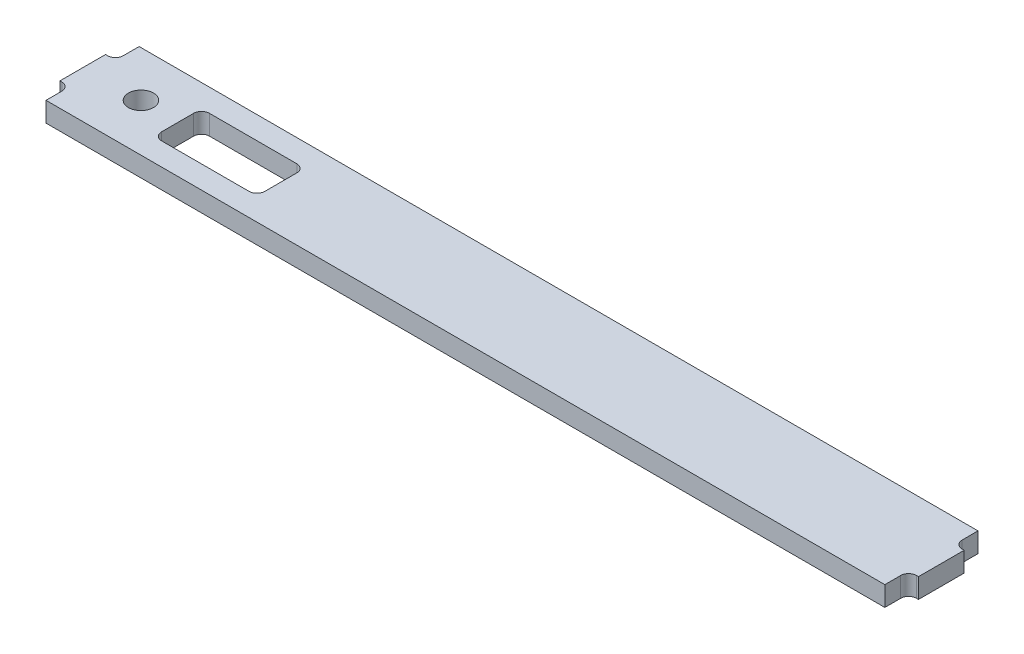
SolidWorks part; units mm, degrees
ref_plane "Front Plane" through (0, 0, 0) normal (0, 0, 1) x (1, 0, 0)
ref_plane "Top Plane" through (0, 0, 0) normal (0, 1, 0) x (1, 0, 0)
ref_plane "Right Plane" through (0, 0, 0) normal (1, 0, 0) x (0, 0, -1)
sketch "Sketch1" plane through (0, 0, 0) normal (0, 1, 0) x (1, 0, 0)
  line L1 (336.55, 37.3714) -> (-336.55, 37.3714)
  line L2 (336.55, 37.3714) -> (336.55, -37.3714)
  line L3 (336.55, -37.3714) -> (-336.55, -37.3714)
  line L4 (-336.55, 37.3714) -> (-336.55, -37.3714)
  line L5 (336.55, 37.3714) -> (-336.55, -37.3714) construction
  line L6 (336.55, -37.3714) -> (-336.55, 37.3714) construction
  point P0 (0, 0)
  dimension "D1" = 673.1
  dimension "D2" = 74.7428
extrude "Boss-Extrude1" add sketch "Sketch1" along normal blind 15.875
sketch "Sketch2" plane through (0, 15.875, 0) normal (0, 1, 0) x (1, 0, 0)
  line L0 (336.55, 37.3714) -> (-336.55, 37.3714) construction
  line L1 (344.4875, 18.3214) -> (-344.4875, 18.3214)
  line L2 (344.4875, 18.3214) -> (344.4875, -18.3214)
  line L3 (344.4875, -18.3214) -> (-344.4875, -18.3214)
  line L4 (-344.4875, 18.3214) -> (-344.4875, -18.3214)
  line L5 (344.4875, 18.3214) -> (-344.4875, -18.3214) construction
  line L6 (344.4875, -18.3214) -> (-344.4875, 18.3214) construction
  line L7 (-336.55, 37.3714) -> (-336.55, -37.3714) construction
  point P0 (0, 0)
  dimension "D1" = 19.05
  dimension "D2" = 7.9375
extrude "Boss-Extrude2" [suppressed] add sketch "Sketch2" against normal up to surface (15.875 mm away) up to face at (0, 0, 0)
fillet "Fillet1" [suppressed] radius 6.35
sketch "Sketch3" plane through (0, 15.875, 0) normal (0, 1, 0) x (1, 0, 0)
  line L0 (-336.55, -37.3714) -> (336.55, -37.3714) construction
  line L2 (-336.55, 37.3714) -> (-336.55, -37.3714) construction
  circle A0 centre (-298.45, 0.7286) radius 10.1
  dimension "D3" = 20.2
  dimension "D1" = 38.1
  dimension "D2" = 38.1
extrude "Cut-Extrude1" cut sketch "Sketch3" against normal through all both and the other way through all
sketch "Sketch4" plane through (0, 15.875, 0) normal (0, 1, 0) x (1, 0, 0)
  line L0 (-336.55, 37.3714) -> (-336.55, -37.3714) construction
  line L1 (-336.55, 18.3214) -> (-344.4875, 18.3214)
  line L2 (-336.55, 18.3214) -> (-336.55, -18.3214)
  line L3 (-336.55, -18.3214) -> (-344.4875, -18.3214)
  line L4 (-344.4875, 18.3214) -> (-344.4875, -18.3214)
  line L5 (336.55, 37.3714) -> (-336.55, 37.3714) construction
  line L6 (-336.55, -37.3714) -> (336.55, -37.3714) construction
  line L7 (0, -5.1837) -> (0, 37.3714) construction
  line L8 (344.4875, 18.3214) -> (344.4875, -18.3214)
  line L9 (336.55, -18.3214) -> (344.4875, -18.3214)
  line L10 (336.55, 18.3214) -> (336.55, -18.3214)
  line L11 (336.55, 18.3214) -> (344.4875, 18.3214)
  dimension "D1" = 19.05
  dimension "D2" = 19.05
  dimension "D3" = 7.9375
  dimension "D4" = 688.975
extrude "Boss-Extrude3" add sketch "Sketch4" against normal up to surface (15.875 mm away) up to face at (-298.45, 0, 9.3714)
fillet "Fillet2" radius 6.35 4 edges at (336.55, 7.9375, 18.3214) (336.55, 7.9375, -18.3214) (-336.55, 7.9375, 18.3214) (-336.55, 7.9375, -18.3214)
sketch "Sketch5" plane through (0, 15.875, 0) normal (0, 1, 0) x (1, 0, 0)
  line L0 (0, 0) -> (-185.4835, 0) construction
  line L1 (-268.2875, -19.177) -> (-185.4835, -19.177)
  line L2 (-268.2875, -19.177) -> (-268.2875, 19.177)
  line L3 (-268.2875, 19.177) -> (-185.4835, 19.177)
  line L4 (-185.4835, -19.177) -> (-185.4835, 19.177)
  line L5 (-344.4875, 18.3214) -> (-344.4875, -18.3214) construction
  dimension "D1" = 82.804
  dimension "D2" = 38.354
  dimension "D3" = 76.2
extrude "Cut-Extrude2" cut sketch "Sketch5" against normal through all both and the other way through all
fillet "Fillet3" radius 6.35 4 edges at (-268.2875, 7.9375, -19.177) (-185.4835, 7.9375, -19.177) (-185.4835, 7.9375, 19.177) (-268.2875, 7.9375, 19.177)
